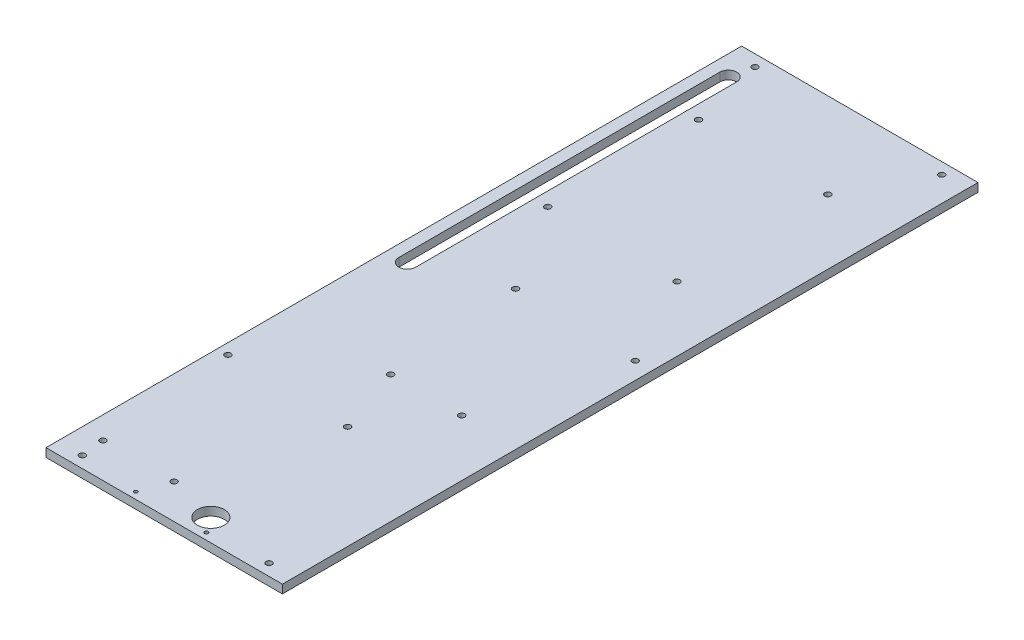
SolidWorks part; units mm, degrees
ref_plane "Front Plane" through (0, 0, 0) normal (0, 0, 1) x (1, 0, 0)
ref_plane "Top Plane" through (0, 0, 0) normal (0, 1, 0) x (1, 0, 0)
ref_plane "Right Plane" through (0, 0, 0) normal (1, 0, 0) x (0, 0, -1)
sketch "Sketch2" plane through (0, 0, 0) normal (0, 0, 1) x (1, 0, 0)
  line L0 (42.8242, -21.393) -> (42.8242, -24.5934)
  line L1 (0, -21.393) -> (0, -24.5934) construction
  line L2 (-46.0758, -24.5934) -> (42.8242, -24.5934)
  line L3 (-46.0758, -21.393) -> (-46.0758, -24.5934)
  line L4 (-46.0758, -21.393) -> (42.8242, -21.393)
  dimension "D1" = 88.9
  dimension "D2" = 3.2004
extrude "Boss-Extrude1" add sketch "Sketch2" along normal blind 261.62 contours L2 L0 L4 L3
sketch "Sketch3" plane through (0, -21.393, 0) normal (0, 1, 0) x (-1, 0, 0)
  line L0 (-42.8242, 259.08) -> (46.0758, 259.08) construction
  line L1 (38.5043, 9.421) -> (38.5043, 0) construction
  line L2 (46.0758, 0) -> (-42.8242, 0) construction
  line L3 (46.0758, 261.62) -> (-42.8242, 261.62) construction
  line L4 (36.73, 257.302) -> (46.0758, 257.302) construction
  line L5 (46.0758, 72.9493) -> (41.6793, 72.9493) construction
  line L6 (35.3293, 12.596) -> (41.6793, 12.596) construction
  line L7 (35.3293, 12.596) -> (35.3293, 133.3026)
  line L8 (35.3293, 133.3026) -> (41.6793, 133.3026) construction
  line L9 (41.6793, 12.596) -> (41.6793, 133.3026)
  line L10 (46.0758, 261.62) -> (-42.8242, 261.62) construction
  line L11 (-11.6838, 259.08) -> (-11.6838, 261.62) construction
  line L12 (-11.6838, 253.3188) -> (-11.6838, 259.08) construction
  line L13 (-7.6198, 253.3188) -> (-11.6838, 253.3188) construction
  line L14 (-42.8242, 261.62) -> (-42.8242, 0) construction
  line L15 (46.0758, 261.62) -> (46.0758, 0) construction
  line L16 (-33.4785, 257.302) -> (-33.4785, 261.62) construction
  line L17 (-33.4785, 257.302) -> (-42.8242, 257.302) construction
  line L18 (36.73, 257.302) -> (36.73, 261.62) construction
  line L19 (-33.4785, 4.318) -> (-42.8242, 4.318) construction
  line L20 (-33.4785, 4.318) -> (-33.4785, 0) construction
  line L21 (46.0758, 0) -> (-42.8242, 0) construction
  line L22 (36.73, 4.318) -> (36.73, 0) construction
  line L23 (36.73, 4.318) -> (46.0758, 4.318) construction
  line L24 (-18.451, 32.1211) -> (-18.451, 0) construction
  line L25 (-42.8242, 32.1211) -> (-18.451, 32.1211) construction
  line L26 (-18.451, 32.1211) -> (30.1646, 32.1211) construction
  line L27 (-18.451, 32.1211) -> (-18.451, 88.8393) construction
  line L28 (30.1646, 32.1211) -> (30.1646, 88.8393) construction
  line L29 (-18.451, 88.8393) -> (30.1646, 88.8393) construction
  line L30 (-42.8242, 122.5046) -> (-36.4214, 122.5046) construction
  line L31 (-36.4214, 122.5046) -> (-36.4214, 0) construction
  line L32 (5.127, 172.9556) -> (9.5159, 121.5883) construction
  line L33 (-21.6121, 172.9556) -> (5.127, 172.9556) construction
  line L34 (60.367, -163.7177) -> (66.7698, -163.7177) construction
  line L35 (66.7698, -163.7177) -> (96.7645, -163.7177) construction
  line L36 (-21.6121, 172.9556) -> (-36.4214, 122.5046) construction
  line L37 (81.5791, -113.2668) -> (108.3182, -113.2668) construction
  line L38 (81.5791, -113.2668) -> (66.7698, -163.7177) construction
  line L39 (76.3923, -158.9273) -> (82.7952, -158.9273) construction
  line L40 (82.7952, -158.9273) -> (112.7898, -158.9273) construction
  line L41 (97.6044, -108.4763) -> (124.3436, -108.4763) construction
  line L42 (97.6044, -108.4763) -> (82.7952, -158.9273) construction
  line L43 (37.7042, 261.62) -> (37.7042, 248.5682) construction
  line L45 (10.9651, 248.5682) -> (37.7042, 248.5682) construction
  line L46 (10.9651, 248.5682) -> (-3.8441, 198.1173) construction
  line L47 (37.7042, 248.5682) -> (46.0758, 248.5682) construction
  line L48 (37.7042, 248.5682) -> (42.0931, 197.2009) construction
  circle A0 centre (14.8338, 259.08) radius 0.6731
  arc A1 (35.3293, 133.3026) -> (41.6793, 133.3026) centre (38.5043, 133.3026) cw
  arc A2 (41.6793, 12.596) -> (35.3293, 12.596) centre (38.5043, 12.596) cw
  circle A3 centre (-11.6838, 259.08) radius 0.6731
  circle A4 centre (-7.6198, 253.3188) radius 5.08
  circle A5 centre (-33.4785, 257.302) radius 1.1303
  circle A6 centre (36.73, 257.302) radius 1.1303
  circle A7 centre (-33.4785, 4.318) radius 1.1303
  circle A8 centre (36.73, 4.318) radius 1.1303
  circle A9 centre (-18.451, 32.1211) radius 1.1303
  circle A10 centre (-18.451, 88.8393) radius 1.1303
  circle A11 centre (30.1646, 88.8393) radius 1.1303
  circle A12 centre (30.1646, 32.1211) radius 1.1303
  circle A13 centre (-21.6121, 172.9556) radius 1.1303
  circle A14 centre (-36.4214, 122.5046) radius 1.1303
  circle A15 centre (5.127, 172.9556) radius 1.1303
  circle A16 centre (9.5159, 121.5883) radius 1.1303
  circle A17 centre (81.5791, -113.2668) radius 1.1303
  circle A18 centre (66.7698, -163.7177) radius 1.1303
  circle A19 centre (108.3182, -113.2668) radius 1.1303
  circle A20 centre (97.6044, -108.4763) radius 1.1303
  circle A21 centre (82.7952, -158.9273) radius 1.1303
  circle A22 centre (124.3436, -108.4763) radius 1.1303
  circle A23 centre (112.7898, -158.9273) radius 1.1303
  circle A24 centre (10.9651, 248.5682) radius 1.1303
  circle A25 centre (-3.8441, 198.1173) radius 1.1303
  circle A26 centre (37.7042, 248.5682) radius 1.1303
  circle A27 centre (42.0931, 197.2009) radius 1.1303
  point P12 (1.6258, 259.08)
  dimension "D5" = 1.3462
  dimension "D9" = 10.16
  dimension "D13" = 2.2606
  dimension "D15" = 9.3458
  dimension "D2" = 4.3965
  dimension "D3" = 120.7066
  dimension "D4" = 6.35
  dimension "D6" = 2.54
  dimension "D7" = 26.5176
  dimension "D8" = 13.208
  dimension "D10" = 5.7612
  dimension "D11" = 4.064
  dimension "D12" = 9.421
  dimension "D14" = 4.318
  dimension "D16" = 24.3732
  dimension "D17" = 32.1211
  dimension "D18" = 48.6156
  dimension "D19" = 56.7182
  dimension "D20" = 6.4028
  dimension "D21" = 122.5046
  dimension "D22" = 51.5544
  dimension "D23" = 106.359
  dimension "D24" = 26.7391
  dimension "D25" = 52.5796
  dimension "D26" = 6.4028
  dimension "D27" = 29.9946
  dimension "D28" = 26.7391
  dimension "D29" = 73.641
  dimension "D30" = 52.5796
  dimension "D31" = 6.4028
  dimension "D32" = 29.9946
  dimension "D33" = 26.7391
  dimension "D34" = 73.641
  dimension "D35" = 52.5796
  dimension "D36" = 13.0518
  dimension "D37" = 106.359
  dimension "D38" = 26.7391
  dimension "D39" = 94.884
  dimension "D40" = 52.5796
  dimension "D41" = 8.3715
  dimension "D42" = 51.5544
  dimension "D43" = 94.884
extrude "Cut-Extrude1" cut sketch "Sketch3" against normal through all
sketch "Sketch4" plane through (0, 0, 0) normal (0, 0, -1) x (-1, 0, 0)
  line L0 (1.6258, -21.393) -> (1.6258, -24.5934) construction
  line L1 (46.0758, -21.393) -> (-42.8242, -21.393) construction
  line L2 (46.0758, -24.5934) -> (-42.8242, -24.5934) construction
sketch "Sketch5" plane through (42.8242, 0, 0) normal (1, 0, 0) x (0, 0, -1)
  line L0 (-130.81, -21.393) -> (-130.81, -24.5934) construction
  line L1 (-261.62, -21.393) -> (0, -21.393) construction
  line L2 (-261.62, -24.5934) -> (0, -24.5934) construction
